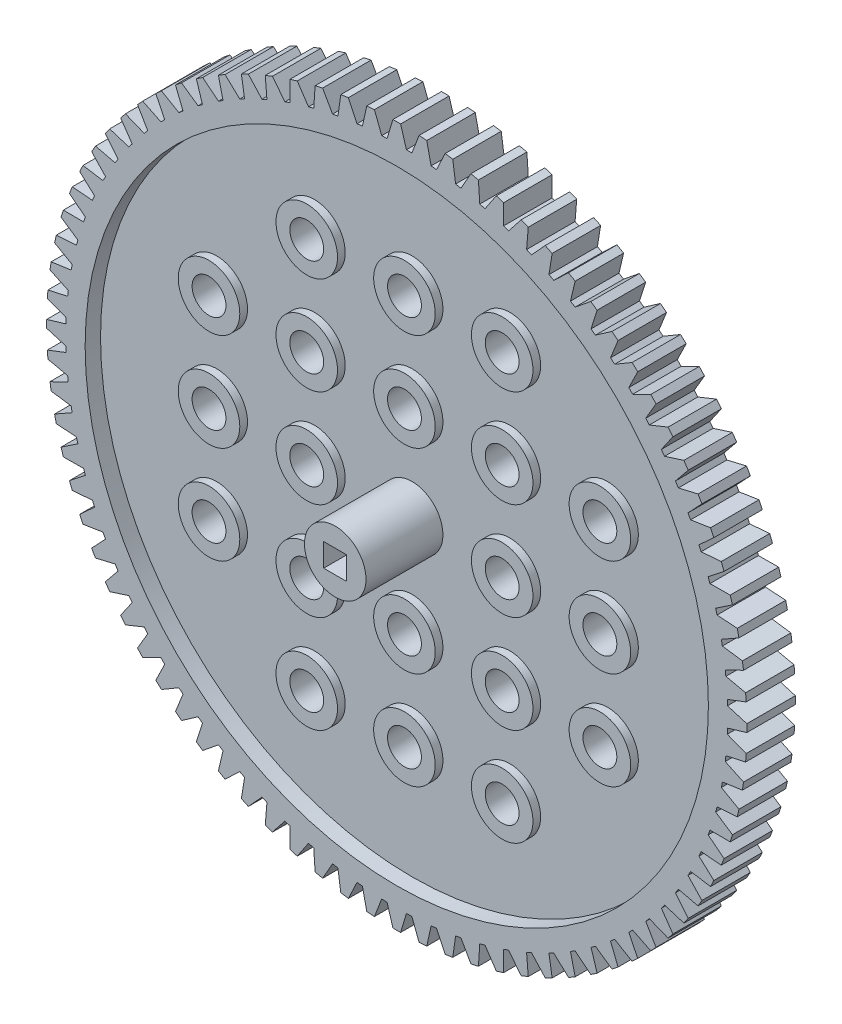
SolidWorks part; units mm, degrees
ref_plane "Front Plane" through (0, 0, 0) normal (0, 0, 1) x (1, 0, 0)
ref_plane "Top Plane" through (0, 0, 0) normal (0, 1, 0) x (1, 0, 0)
ref_plane "Right Plane" through (0, 0, 0) normal (1, 0, 0) x (0, 0, -1)
sketch "Sketch1" plane through (0, 0, 0) normal (0, 0, 1) x (1, 0, 0)
  line L0 (0, 45.5) -> (0, 43)
  line L1 (1.5, -1.5) -> (-1.5, -1.5)
  line L2 (1.5, -1.5) -> (1.5, 1.5)
  line L3 (1.5, 1.5) -> (-1.5, 1.5)
  line L4 (-1.5, -1.5) -> (-1.5, 1.5)
  line L5 (1.5, -1.5) -> (-1.5, 1.5) construction
  line L6 (1.5, 1.5) -> (-1.5, -1.5) construction
  line L7 (-1.25, 43) -> (1.25, 43) construction
  line L8 (-0.5, 45.5) -> (0.5, 45.5)
  line L9 (-1.25, 43) -> (-0.5, 45.5)
  line L10 (1.25, 43) -> (0.5, 45.5)
  line L11 (-1.25, 43) -> (-1.2555, 42.9817)
  line L12 (1.25, 43) -> (1.2555, 42.9817)
  line L13 (1.9669, 42.9732) -> (2.9016, 45.4101)
  line L14 (2.9016, 45.4101) -> (3.8988, 45.3354)
  line L15 (4.4599, 42.7864) -> (3.8988, 45.3354)
  line L16 (1.9669, 42.9732) -> (1.96, 42.9553)
  line L17 (4.4599, 42.7864) -> (4.464, 42.7677)
  line L18 (5.1728, 42.706) -> (6.287, 45.0663)
  line L19 (6.287, 45.0663) -> (7.2758, 44.9173)
  line L20 (7.6449, 42.3334) -> (7.2758, 44.9173)
  line L21 (5.1728, 42.706) -> (5.1646, 42.6887)
  line L22 (7.6449, 42.3334) -> (7.6476, 42.3145)
  line L23 (8.3497, 42.2001) -> (9.6372, 44.4705)
  line L24 (9.6372, 44.4705) -> (10.6122, 44.248)
  line L25 (10.7871, 41.6437) -> (10.6122, 44.248)
  line L26 (8.3497, 42.2001) -> (8.3403, 42.1834)
  line L27 (10.7871, 41.6437) -> (10.7883, 41.6247)
  line L28 (11.48, 41.4581) -> (12.9336, 43.6259)
  line L29 (12.9336, 43.6259) -> (13.8891, 43.3312)
  line L30 (13.8689, 40.7212) -> (13.8891, 43.3312)
  line L31 (11.48, 41.4581) -> (11.4693, 41.4422)
  line L32 (13.8689, 40.7212) -> (13.8688, 40.702)
  line L33 (14.5461, 40.4842) -> (16.1576, 42.5374)
  line L34 (16.1576, 42.5374) -> (17.0885, 42.1721)
  line L35 (16.8733, 39.5709) -> (17.0885, 42.1721)
  line L36 (14.5461, 40.4842) -> (14.5343, 40.4692)
  line L37 (16.8733, 39.5709) -> (16.8717, 39.5518)
  line L38 (17.5308, 39.284) -> (19.2912, 41.211)
  line L39 (19.2912, 41.211) -> (20.1922, 40.7771)
  line L40 (19.7832, 38.1993) -> (20.1922, 40.7771)
  line L41 (17.5308, 39.284) -> (17.5179, 39.2699)
  line L42 (19.7832, 38.1993) -> (19.7802, 38.1804)
  line L43 (20.4175, 37.8641) -> (22.317, 39.6542)
  line L44 (22.317, 39.6542) -> (23.183, 39.1542)
  line L45 (22.5825, 36.6141) -> (23.183, 39.1542)
  line L46 (20.4175, 37.8641) -> (20.4035, 37.851)
  line L47 (22.5825, 36.6141) -> (22.5781, 36.5955)
  line L48 (23.19, 36.2324) -> (25.2179, 37.8755)
  line L49 (25.2179, 37.8755) -> (26.0442, 37.3122)
  line L50 (25.2556, 34.8241) -> (26.0442, 37.3122)
  line L51 (23.19, 36.2324) -> (23.1751, 36.2204)
  line L52 (25.2556, 34.8241) -> (25.2498, 34.8059)
  line L53 (25.8328, 34.3981) -> (27.9779, 35.8851)
  line L54 (27.9779, 35.8851) -> (28.7597, 35.2616)
  line L55 (27.7874, 32.8394) -> (28.7597, 35.2616)
  line L56 (25.8328, 34.3981) -> (25.817, 34.3872)
  line L57 (27.7874, 32.8394) -> (27.7802, 32.8216)
  line L58 (28.3311, 32.3714) -> (30.5813, 33.6939)
  line L59 (30.5813, 33.6939) -> (31.3144, 33.0138)
  line L60 (30.1637, 30.671) -> (31.3144, 33.0138)
  line L61 (28.3311, 32.3714) -> (28.3146, 32.3617)
  line L62 (30.1637, 30.671) -> (30.1553, 30.6538)
  line L63 (30.671, 30.1637) -> (33.0138, 31.3144)
  line L64 (33.0138, 31.3144) -> (33.6939, 30.5813)
  line L65 (32.3714, 28.3311) -> (33.6939, 30.5813)
  line L66 (30.671, 30.1637) -> (30.6538, 30.1553)
  line L67 (32.3714, 28.3311) -> (32.3617, 28.3146)
  line L68 (32.8394, 27.7874) -> (35.2616, 28.7597)
  line L69 (35.2616, 28.7597) -> (35.8851, 27.9779)
  line L70 (34.3981, 25.8328) -> (35.8851, 27.9779)
  line L71 (32.8394, 27.7874) -> (32.8216, 27.7802)
  line L72 (34.3981, 25.8328) -> (34.3872, 25.817)
  line L73 (34.8241, 25.2556) -> (37.3122, 26.0442)
  line L74 (37.3122, 26.0442) -> (37.8755, 25.2179)
  line L75 (36.2324, 23.19) -> (37.8755, 25.2179)
  line L76 (34.8241, 25.2556) -> (34.8059, 25.2498)
  line L77 (36.2324, 23.19) -> (36.2204, 23.1751)
  line L78 (36.6141, 22.5825) -> (39.1542, 23.183)
  line L79 (39.1542, 23.183) -> (39.6542, 22.317)
  line L80 (37.8641, 20.4175) -> (39.6542, 22.317)
  line L81 (36.6141, 22.5825) -> (36.5955, 22.5781)
  line L82 (37.8641, 20.4175) -> (37.851, 20.4035)
  line L83 (38.1993, 19.7832) -> (40.7771, 20.1922)
  line L84 (40.7771, 20.1922) -> (41.211, 19.2912)
  line L85 (39.284, 17.5308) -> (41.211, 19.2912)
  line L86 (38.1993, 19.7832) -> (38.1804, 19.7802)
  line L87 (39.284, 17.5308) -> (39.2699, 17.5179)
  line L88 (39.5709, 16.8733) -> (42.1721, 17.0885)
  line L89 (42.1721, 17.0885) -> (42.5374, 16.1576)
  line L90 (40.4842, 14.5461) -> (42.5374, 16.1576)
  line L91 (39.5709, 16.8733) -> (39.5518, 16.8717)
  line L92 (40.4842, 14.5461) -> (40.4692, 14.5343)
  line L93 (40.7212, 13.8689) -> (43.3312, 13.8891)
  line L94 (43.3312, 13.8891) -> (43.6259, 12.9336)
  line L95 (41.4581, 11.48) -> (43.6259, 12.9336)
  line L96 (40.7212, 13.8689) -> (40.702, 13.8688)
  line L97 (41.4581, 11.48) -> (41.4422, 11.4693)
  line L98 (41.6437, 10.7871) -> (44.248, 10.6122)
  line L99 (44.248, 10.6122) -> (44.4705, 9.6372)
  line L100 (42.2001, 8.3497) -> (44.4705, 9.6372)
  line L101 (41.6437, 10.7871) -> (41.6247, 10.7883)
  line L102 (42.2001, 8.3497) -> (42.1834, 8.3403)
  line L103 (42.3334, 7.6449) -> (44.9173, 7.2758)
  line L104 (44.9173, 7.2758) -> (45.0663, 6.287)
  line L105 (42.706, 5.1728) -> (45.0663, 6.287)
  line L106 (42.3334, 7.6449) -> (42.3145, 7.6476)
  line L107 (42.706, 5.1728) -> (42.6887, 5.1646)
  line L108 (42.7864, 4.4599) -> (45.3354, 3.8988)
  line L109 (45.3354, 3.8988) -> (45.4101, 2.9016)
  line L110 (42.9732, 1.9669) -> (45.4101, 2.9016)
  line L111 (42.7864, 4.4599) -> (42.7677, 4.464)
  line L112 (42.9732, 1.9669) -> (42.9553, 1.96)
  line L113 (43, 1.25) -> (45.5, 0.5)
  line L114 (45.5, 0.5) -> (45.5, -0.5)
  line L115 (43, -1.25) -> (45.5, -0.5)
  line L116 (43, 1.25) -> (42.9817, 1.2555)
  line L117 (43, -1.25) -> (42.9817, -1.2555)
  line L118 (42.9732, -1.9669) -> (45.4101, -2.9016)
  line L119 (45.4101, -2.9016) -> (45.3354, -3.8988)
  line L120 (42.7864, -4.4599) -> (45.3354, -3.8988)
  line L121 (42.9732, -1.9669) -> (42.9553, -1.96)
  line L122 (42.7864, -4.4599) -> (42.7677, -4.464)
  line L123 (42.706, -5.1728) -> (45.0663, -6.287)
  line L124 (45.0663, -6.287) -> (44.9173, -7.2758)
  line L125 (42.3334, -7.6449) -> (44.9173, -7.2758)
  line L126 (42.706, -5.1728) -> (42.6887, -5.1646)
  line L127 (42.3334, -7.6449) -> (42.3145, -7.6476)
  line L128 (42.2001, -8.3497) -> (44.4705, -9.6372)
  line L129 (44.4705, -9.6372) -> (44.248, -10.6122)
  line L130 (41.6437, -10.7871) -> (44.248, -10.6122)
  line L131 (42.2001, -8.3497) -> (42.1834, -8.3403)
  line L132 (41.6437, -10.7871) -> (41.6247, -10.7883)
  line L133 (41.4581, -11.48) -> (43.6259, -12.9336)
  line L134 (43.6259, -12.9336) -> (43.3312, -13.8891)
  line L135 (40.7212, -13.8689) -> (43.3312, -13.8891)
  line L136 (41.4581, -11.48) -> (41.4422, -11.4693)
  line L137 (40.7212, -13.8689) -> (40.702, -13.8688)
  line L138 (40.4842, -14.5461) -> (42.5374, -16.1576)
  line L139 (42.5374, -16.1576) -> (42.1721, -17.0885)
  line L140 (39.5709, -16.8733) -> (42.1721, -17.0885)
  line L141 (40.4842, -14.5461) -> (40.4692, -14.5343)
  line L142 (39.5709, -16.8733) -> (39.5518, -16.8717)
  line L143 (39.284, -17.5308) -> (41.211, -19.2912)
  line L144 (41.211, -19.2912) -> (40.7771, -20.1922)
  line L145 (38.1993, -19.7832) -> (40.7771, -20.1922)
  line L146 (39.284, -17.5308) -> (39.2699, -17.5179)
  line L147 (38.1993, -19.7832) -> (38.1804, -19.7802)
  line L148 (37.8641, -20.4175) -> (39.6542, -22.317)
  line L149 (39.6542, -22.317) -> (39.1542, -23.183)
  line L150 (36.6141, -22.5825) -> (39.1542, -23.183)
  line L151 (37.8641, -20.4175) -> (37.851, -20.4035)
  line L152 (36.6141, -22.5825) -> (36.5955, -22.5781)
  line L153 (36.2324, -23.19) -> (37.8755, -25.2179)
  line L154 (37.8755, -25.2179) -> (37.3122, -26.0442)
  line L155 (34.8241, -25.2556) -> (37.3122, -26.0442)
  line L156 (36.2324, -23.19) -> (36.2204, -23.1751)
  line L157 (34.8241, -25.2556) -> (34.8059, -25.2498)
  line L158 (34.3981, -25.8328) -> (35.8851, -27.9779)
  line L159 (35.8851, -27.9779) -> (35.2616, -28.7597)
  line L160 (32.8394, -27.7874) -> (35.2616, -28.7597)
  line L161 (34.3981, -25.8328) -> (34.3872, -25.817)
  line L162 (32.8394, -27.7874) -> (32.8216, -27.7802)
  line L163 (32.3714, -28.3311) -> (33.6939, -30.5813)
  line L164 (33.6939, -30.5813) -> (33.0138, -31.3144)
  line L165 (30.671, -30.1637) -> (33.0138, -31.3144)
  line L166 (32.3714, -28.3311) -> (32.3617, -28.3146)
  line L167 (30.671, -30.1637) -> (30.6538, -30.1553)
  line L168 (30.1637, -30.671) -> (31.3144, -33.0138)
  line L169 (31.3144, -33.0138) -> (30.5813, -33.6939)
  line L170 (28.3311, -32.3714) -> (30.5813, -33.6939)
  line L171 (30.1637, -30.671) -> (30.1553, -30.6538)
  line L172 (28.3311, -32.3714) -> (28.3146, -32.3617)
  line L173 (27.7874, -32.8394) -> (28.7597, -35.2616)
  line L174 (28.7597, -35.2616) -> (27.9779, -35.8851)
  line L175 (25.8328, -34.3981) -> (27.9779, -35.8851)
  line L176 (27.7874, -32.8394) -> (27.7802, -32.8216)
  line L177 (25.8328, -34.3981) -> (25.817, -34.3872)
  line L178 (25.2556, -34.8241) -> (26.0442, -37.3122)
  line L179 (26.0442, -37.3122) -> (25.2179, -37.8755)
  line L180 (23.19, -36.2324) -> (25.2179, -37.8755)
  line L181 (25.2556, -34.8241) -> (25.2498, -34.8059)
  line L182 (23.19, -36.2324) -> (23.1751, -36.2204)
  line L183 (22.5825, -36.6141) -> (23.183, -39.1542)
  line L184 (23.183, -39.1542) -> (22.317, -39.6542)
  line L185 (20.4175, -37.8641) -> (22.317, -39.6542)
  line L186 (22.5825, -36.6141) -> (22.5781, -36.5955)
  line L187 (20.4175, -37.8641) -> (20.4035, -37.851)
  line L188 (19.7832, -38.1993) -> (20.1922, -40.7771)
  line L189 (20.1922, -40.7771) -> (19.2912, -41.211)
  line L190 (17.5308, -39.284) -> (19.2912, -41.211)
  line L191 (19.7832, -38.1993) -> (19.7802, -38.1804)
  line L192 (17.5308, -39.284) -> (17.5179, -39.2699)
  line L193 (16.8733, -39.5709) -> (17.0885, -42.1721)
  line L194 (17.0885, -42.1721) -> (16.1576, -42.5374)
  line L195 (14.5461, -40.4842) -> (16.1576, -42.5374)
  line L196 (16.8733, -39.5709) -> (16.8717, -39.5518)
  line L197 (14.5461, -40.4842) -> (14.5343, -40.4692)
  line L198 (13.8689, -40.7212) -> (13.8891, -43.3312)
  line L199 (13.8891, -43.3312) -> (12.9336, -43.6259)
  line L200 (11.48, -41.4581) -> (12.9336, -43.6259)
  line L201 (13.8689, -40.7212) -> (13.8688, -40.702)
  line L202 (11.48, -41.4581) -> (11.4693, -41.4422)
  line L203 (10.7871, -41.6437) -> (10.6122, -44.248)
  line L204 (10.6122, -44.248) -> (9.6372, -44.4705)
  line L205 (8.3497, -42.2001) -> (9.6372, -44.4705)
  line L206 (10.7871, -41.6437) -> (10.7883, -41.6247)
  line L207 (8.3497, -42.2001) -> (8.3403, -42.1834)
  line L208 (7.6449, -42.3334) -> (7.2758, -44.9173)
  line L209 (7.2758, -44.9173) -> (6.287, -45.0663)
  line L210 (5.1728, -42.706) -> (6.287, -45.0663)
  line L211 (7.6449, -42.3334) -> (7.6476, -42.3145)
  line L212 (5.1728, -42.706) -> (5.1646, -42.6887)
  line L213 (4.4599, -42.7864) -> (3.8988, -45.3354)
  line L214 (3.8988, -45.3354) -> (2.9016, -45.4101)
  line L215 (1.9669, -42.9732) -> (2.9016, -45.4101)
  line L216 (4.4599, -42.7864) -> (4.464, -42.7677)
  line L217 (1.9669, -42.9732) -> (1.96, -42.9553)
  line L218 (1.25, -43) -> (0.5, -45.5)
  line L219 (0.5, -45.5) -> (-0.5, -45.5)
  line L220 (-1.25, -43) -> (-0.5, -45.5)
  line L221 (1.25, -43) -> (1.2555, -42.9817)
  line L222 (-1.25, -43) -> (-1.2555, -42.9817)
  line L223 (-1.9669, -42.9732) -> (-2.9016, -45.4101)
  line L224 (-2.9016, -45.4101) -> (-3.8988, -45.3354)
  line L225 (-4.4599, -42.7864) -> (-3.8988, -45.3354)
  line L226 (-1.9669, -42.9732) -> (-1.96, -42.9553)
  line L227 (-4.4599, -42.7864) -> (-4.464, -42.7677)
  line L228 (-5.1728, -42.706) -> (-6.287, -45.0663)
  line L229 (-6.287, -45.0663) -> (-7.2758, -44.9173)
  line L230 (-7.6449, -42.3334) -> (-7.2758, -44.9173)
  line L231 (-5.1728, -42.706) -> (-5.1646, -42.6887)
  line L232 (-7.6449, -42.3334) -> (-7.6476, -42.3145)
  line L233 (-8.3497, -42.2001) -> (-9.6372, -44.4705)
  line L234 (-9.6372, -44.4705) -> (-10.6122, -44.248)
  line L235 (-10.7871, -41.6437) -> (-10.6122, -44.248)
  line L236 (-8.3497, -42.2001) -> (-8.3403, -42.1834)
  line L237 (-10.7871, -41.6437) -> (-10.7883, -41.6247)
  line L238 (-11.48, -41.4581) -> (-12.9336, -43.6259)
  line L239 (-12.9336, -43.6259) -> (-13.8891, -43.3312)
  line L240 (-13.8689, -40.7212) -> (-13.8891, -43.3312)
  line L241 (-11.48, -41.4581) -> (-11.4693, -41.4422)
  line L242 (-13.8689, -40.7212) -> (-13.8688, -40.702)
  line L243 (-14.5461, -40.4842) -> (-16.1576, -42.5374)
  line L244 (-16.1576, -42.5374) -> (-17.0885, -42.1721)
  line L245 (-16.8733, -39.5709) -> (-17.0885, -42.1721)
  line L246 (-14.5461, -40.4842) -> (-14.5343, -40.4692)
  line L247 (-16.8733, -39.5709) -> (-16.8717, -39.5518)
  line L248 (-17.5308, -39.284) -> (-19.2912, -41.211)
  line L249 (-19.2912, -41.211) -> (-20.1922, -40.7771)
  line L250 (-19.7832, -38.1993) -> (-20.1922, -40.7771)
  line L251 (-17.5308, -39.284) -> (-17.5179, -39.2699)
  line L252 (-19.7832, -38.1993) -> (-19.7802, -38.1804)
  line L253 (-20.4175, -37.8641) -> (-22.317, -39.6542)
  line L254 (-22.317, -39.6542) -> (-23.183, -39.1542)
  line L255 (-22.5825, -36.6141) -> (-23.183, -39.1542)
  line L256 (-20.4175, -37.8641) -> (-20.4035, -37.851)
  line L257 (-22.5825, -36.6141) -> (-22.5781, -36.5955)
  line L258 (-23.19, -36.2324) -> (-25.2179, -37.8755)
  line L259 (-25.2179, -37.8755) -> (-26.0442, -37.3122)
  line L260 (-25.2556, -34.8241) -> (-26.0442, -37.3122)
  line L261 (-23.19, -36.2324) -> (-23.1751, -36.2204)
  line L262 (-25.2556, -34.8241) -> (-25.2498, -34.8059)
  line L263 (-25.8328, -34.3981) -> (-27.9779, -35.8851)
  line L264 (-27.9779, -35.8851) -> (-28.7597, -35.2616)
  line L265 (-27.7874, -32.8394) -> (-28.7597, -35.2616)
  line L266 (-25.8328, -34.3981) -> (-25.817, -34.3872)
  line L267 (-27.7874, -32.8394) -> (-27.7802, -32.8216)
  line L268 (-28.3311, -32.3714) -> (-30.5813, -33.6939)
  line L269 (-30.5813, -33.6939) -> (-31.3144, -33.0138)
  line L270 (-30.1637, -30.671) -> (-31.3144, -33.0138)
  line L271 (-28.3311, -32.3714) -> (-28.3146, -32.3617)
  line L272 (-30.1637, -30.671) -> (-30.1553, -30.6538)
  line L273 (-30.671, -30.1637) -> (-33.0138, -31.3144)
  line L274 (-33.0138, -31.3144) -> (-33.6939, -30.5813)
  line L275 (-32.3714, -28.3311) -> (-33.6939, -30.5813)
  line L276 (-30.671, -30.1637) -> (-30.6538, -30.1553)
  line L277 (-32.3714, -28.3311) -> (-32.3617, -28.3146)
  line L278 (-32.8394, -27.7874) -> (-35.2616, -28.7597)
  line L279 (-35.2616, -28.7597) -> (-35.8851, -27.9779)
  line L280 (-34.3981, -25.8328) -> (-35.8851, -27.9779)
  line L281 (-32.8394, -27.7874) -> (-32.8216, -27.7802)
  line L282 (-34.3981, -25.8328) -> (-34.3872, -25.817)
  line L283 (-34.8241, -25.2556) -> (-37.3122, -26.0442)
  line L284 (-37.3122, -26.0442) -> (-37.8755, -25.2179)
  line L285 (-36.2324, -23.19) -> (-37.8755, -25.2179)
  line L286 (-34.8241, -25.2556) -> (-34.8059, -25.2498)
  line L287 (-36.2324, -23.19) -> (-36.2204, -23.1751)
  line L288 (-36.6141, -22.5825) -> (-39.1542, -23.183)
  line L289 (-39.1542, -23.183) -> (-39.6542, -22.317)
  line L290 (-37.8641, -20.4175) -> (-39.6542, -22.317)
  line L291 (-36.6141, -22.5825) -> (-36.5955, -22.5781)
  line L292 (-37.8641, -20.4175) -> (-37.851, -20.4035)
  line L293 (-38.1993, -19.7832) -> (-40.7771, -20.1922)
  line L294 (-40.7771, -20.1922) -> (-41.211, -19.2912)
  line L295 (-39.284, -17.5308) -> (-41.211, -19.2912)
  line L296 (-38.1993, -19.7832) -> (-38.1804, -19.7802)
  line L297 (-39.284, -17.5308) -> (-39.2699, -17.5179)
  line L298 (-39.5709, -16.8733) -> (-42.1721, -17.0885)
  line L299 (-42.1721, -17.0885) -> (-42.5374, -16.1576)
  line L300 (-40.4842, -14.5461) -> (-42.5374, -16.1576)
  line L301 (-39.5709, -16.8733) -> (-39.5518, -16.8717)
  line L302 (-40.4842, -14.5461) -> (-40.4692, -14.5343)
  line L303 (-40.7212, -13.8689) -> (-43.3312, -13.8891)
  line L304 (-43.3312, -13.8891) -> (-43.6259, -12.9336)
  line L305 (-41.4581, -11.48) -> (-43.6259, -12.9336)
  line L306 (-40.7212, -13.8689) -> (-40.702, -13.8688)
  line L307 (-41.4581, -11.48) -> (-41.4422, -11.4693)
  line L308 (-41.6437, -10.7871) -> (-44.248, -10.6122)
  line L309 (-44.248, -10.6122) -> (-44.4705, -9.6372)
  line L310 (-42.2001, -8.3497) -> (-44.4705, -9.6372)
  line L311 (-41.6437, -10.7871) -> (-41.6247, -10.7883)
  line L312 (-42.2001, -8.3497) -> (-42.1834, -8.3403)
  line L313 (-42.3334, -7.6449) -> (-44.9173, -7.2758)
  line L314 (-44.9173, -7.2758) -> (-45.0663, -6.287)
  line L315 (-42.706, -5.1728) -> (-45.0663, -6.287)
  line L316 (-42.3334, -7.6449) -> (-42.3145, -7.6476)
  line L317 (-42.706, -5.1728) -> (-42.6887, -5.1646)
  line L318 (-42.7864, -4.4599) -> (-45.3354, -3.8988)
  line L319 (-45.3354, -3.8988) -> (-45.4101, -2.9016)
  line L320 (-42.9732, -1.9669) -> (-45.4101, -2.9016)
  line L321 (-42.7864, -4.4599) -> (-42.7677, -4.464)
  line L322 (-42.9732, -1.9669) -> (-42.9553, -1.96)
  line L323 (-43, -1.25) -> (-45.5, -0.5)
  line L324 (-45.5, -0.5) -> (-45.5, 0.5)
  line L325 (-43, 1.25) -> (-45.5, 0.5)
  line L326 (-43, -1.25) -> (-42.9817, -1.2555)
  line L327 (-43, 1.25) -> (-42.9817, 1.2555)
  line L328 (-42.9732, 1.9669) -> (-45.4101, 2.9016)
  line L329 (-45.4101, 2.9016) -> (-45.3354, 3.8988)
  line L330 (-42.7864, 4.4599) -> (-45.3354, 3.8988)
  line L331 (-42.9732, 1.9669) -> (-42.9553, 1.96)
  line L332 (-42.7864, 4.4599) -> (-42.7677, 4.464)
  line L333 (-42.706, 5.1728) -> (-45.0663, 6.287)
  line L334 (-45.0663, 6.287) -> (-44.9173, 7.2758)
  line L335 (-42.3334, 7.6449) -> (-44.9173, 7.2758)
  line L336 (-42.706, 5.1728) -> (-42.6887, 5.1646)
  line L337 (-42.3334, 7.6449) -> (-42.3145, 7.6476)
  line L338 (-42.2001, 8.3497) -> (-44.4705, 9.6372)
  line L339 (-44.4705, 9.6372) -> (-44.248, 10.6122)
  line L340 (-41.6437, 10.7871) -> (-44.248, 10.6122)
  line L341 (-42.2001, 8.3497) -> (-42.1834, 8.3403)
  line L342 (-41.6437, 10.7871) -> (-41.6247, 10.7883)
  line L343 (-41.4581, 11.48) -> (-43.6259, 12.9336)
  line L344 (-43.6259, 12.9336) -> (-43.3312, 13.8891)
  line L345 (-40.7212, 13.8689) -> (-43.3312, 13.8891)
  line L346 (-41.4581, 11.48) -> (-41.4422, 11.4693)
  line L347 (-40.7212, 13.8689) -> (-40.702, 13.8688)
  line L348 (-40.4842, 14.5461) -> (-42.5374, 16.1576)
  line L349 (-42.5374, 16.1576) -> (-42.1721, 17.0885)
  line L350 (-39.5709, 16.8733) -> (-42.1721, 17.0885)
  line L351 (-40.4842, 14.5461) -> (-40.4692, 14.5343)
  line L352 (-39.5709, 16.8733) -> (-39.5518, 16.8717)
  line L353 (-39.284, 17.5308) -> (-41.211, 19.2912)
  line L354 (-41.211, 19.2912) -> (-40.7771, 20.1922)
  line L355 (-38.1993, 19.7832) -> (-40.7771, 20.1922)
  line L356 (-39.284, 17.5308) -> (-39.2699, 17.5179)
  line L357 (-38.1993, 19.7832) -> (-38.1804, 19.7802)
  line L358 (-37.8641, 20.4175) -> (-39.6542, 22.317)
  line L359 (-39.6542, 22.317) -> (-39.1542, 23.183)
  line L360 (-36.6141, 22.5825) -> (-39.1542, 23.183)
  line L361 (-37.8641, 20.4175) -> (-37.851, 20.4035)
  line L362 (-36.6141, 22.5825) -> (-36.5955, 22.5781)
  line L363 (-36.2324, 23.19) -> (-37.8755, 25.2179)
  line L364 (-37.8755, 25.2179) -> (-37.3122, 26.0442)
  line L365 (-34.8241, 25.2556) -> (-37.3122, 26.0442)
  line L366 (-36.2324, 23.19) -> (-36.2204, 23.1751)
  line L367 (-34.8241, 25.2556) -> (-34.8059, 25.2498)
  line L368 (-34.3981, 25.8328) -> (-35.8851, 27.9779)
  line L369 (-35.8851, 27.9779) -> (-35.2616, 28.7597)
  line L370 (-32.8394, 27.7874) -> (-35.2616, 28.7597)
  line L371 (-34.3981, 25.8328) -> (-34.3872, 25.817)
  line L372 (-32.8394, 27.7874) -> (-32.8216, 27.7802)
  line L373 (-32.3714, 28.3311) -> (-33.6939, 30.5813)
  line L374 (-33.6939, 30.5813) -> (-33.0138, 31.3144)
  line L375 (-30.671, 30.1637) -> (-33.0138, 31.3144)
  line L376 (-32.3714, 28.3311) -> (-32.3617, 28.3146)
  line L377 (-30.671, 30.1637) -> (-30.6538, 30.1553)
  line L378 (-30.1637, 30.671) -> (-31.3144, 33.0138)
  line L379 (-31.3144, 33.0138) -> (-30.5813, 33.6939)
  line L380 (-28.3311, 32.3714) -> (-30.5813, 33.6939)
  line L381 (-30.1637, 30.671) -> (-30.1553, 30.6538)
  line L382 (-28.3311, 32.3714) -> (-28.3146, 32.3617)
  line L383 (-27.7874, 32.8394) -> (-28.7597, 35.2616)
  line L384 (-28.7597, 35.2616) -> (-27.9779, 35.8851)
  line L385 (-25.8328, 34.3981) -> (-27.9779, 35.8851)
  line L386 (-27.7874, 32.8394) -> (-27.7802, 32.8216)
  line L387 (-25.8328, 34.3981) -> (-25.817, 34.3872)
  line L388 (-25.2556, 34.8241) -> (-26.0442, 37.3122)
  line L389 (-26.0442, 37.3122) -> (-25.2179, 37.8755)
  line L390 (-23.19, 36.2324) -> (-25.2179, 37.8755)
  line L391 (-25.2556, 34.8241) -> (-25.2498, 34.8059)
  line L392 (-23.19, 36.2324) -> (-23.1751, 36.2204)
  line L393 (-22.5825, 36.6141) -> (-23.183, 39.1542)
  line L394 (-23.183, 39.1542) -> (-22.317, 39.6542)
  line L395 (-20.4175, 37.8641) -> (-22.317, 39.6542)
  line L396 (-22.5825, 36.6141) -> (-22.5781, 36.5955)
  line L397 (-20.4175, 37.8641) -> (-20.4035, 37.851)
  line L398 (-19.7832, 38.1993) -> (-20.1922, 40.7771)
  line L399 (-20.1922, 40.7771) -> (-19.2912, 41.211)
  line L400 (-17.5308, 39.284) -> (-19.2912, 41.211)
  line L401 (-19.7832, 38.1993) -> (-19.7802, 38.1804)
  line L402 (-17.5308, 39.284) -> (-17.5179, 39.2699)
  line L403 (-16.8733, 39.5709) -> (-17.0885, 42.1721)
  line L404 (-17.0885, 42.1721) -> (-16.1576, 42.5374)
  line L405 (-14.5461, 40.4842) -> (-16.1576, 42.5374)
  line L406 (-16.8733, 39.5709) -> (-16.8717, 39.5518)
  line L407 (-14.5461, 40.4842) -> (-14.5343, 40.4692)
  line L408 (-13.8689, 40.7212) -> (-13.8891, 43.3312)
  line L409 (-13.8891, 43.3312) -> (-12.9336, 43.6259)
  line L410 (-11.48, 41.4581) -> (-12.9336, 43.6259)
  line L411 (-13.8689, 40.7212) -> (-13.8688, 40.702)
  line L412 (-11.48, 41.4581) -> (-11.4693, 41.4422)
  line L413 (-10.7871, 41.6437) -> (-10.6122, 44.248)
  line L414 (-10.6122, 44.248) -> (-9.6372, 44.4705)
  line L415 (-8.3497, 42.2001) -> (-9.6372, 44.4705)
  line L416 (-10.7871, 41.6437) -> (-10.7883, 41.6247)
  line L417 (-8.3497, 42.2001) -> (-8.3403, 42.1834)
  line L418 (-7.6449, 42.3334) -> (-7.2758, 44.9173)
  line L419 (-7.2758, 44.9173) -> (-6.287, 45.0663)
  line L420 (-5.1728, 42.706) -> (-6.287, 45.0663)
  line L421 (-7.6449, 42.3334) -> (-7.6476, 42.3145)
  line L422 (-5.1728, 42.706) -> (-5.1646, 42.6887)
  line L423 (-4.4599, 42.7864) -> (-3.8988, 45.3354)
  line L424 (-3.8988, 45.3354) -> (-2.9016, 45.4101)
  line L425 (-1.9669, 42.9732) -> (-2.9016, 45.4101)
  line L426 (-4.4599, 42.7864) -> (-4.464, 42.7677)
  line L427 (-1.9669, 42.9732) -> (-1.96, 42.9553)
  circle A0 centre (0, 0) radius 45.5 construction
  circle A1 centre (0, 0) radius 40.5
  circle A2 centre (0, 0) radius 43
  point P0 (0, 0)
  point P13 (0, 45.5)
  point P15 (0, 43)
  point P521 (0, 0)
  dimension "D2" = 91
  dimension "D3" = 81
  dimension "D1" = 3
  dimension "D4" = 2.5
  dimension "D5" = 2.5
  dimension "D6" = 1
  dimension "D7" = 84
extrude "Boss-Extrude1" add sketch "Sketch1" along normal blind 6.3 contours A2 L232 L230 L229 L228 L231 | A2 L227 L225 L224 L223 L226 | A2 L222 L220 L219 L218 L221 | A2 L217 L215 L214 L213 L216 | A2 L212 L210 L209 L208 L211 | A2 L207 L205 L204 L203 L206 | A2 L202 L200 L199 L198 L201 | A2 L197 L195 L194 L193 L196 | A2 L192 L190 L189 L188 L191 | A2 L187 L185 L184 L183 L186 | A2 L182 L180 L179 L178 L181 | A2 L177 L175 L174 L173 L176 | A2 L172 L170 L169 L168 L171 | A2 L167 L165 L164 L163 L166 | A2 L162 L160 L159 L158 L161 | A2 L157 L155 L154 L153 L156 | A2 L152 L150 L149 L148 L151 | A2 L147 L145 L144 L143 L146 | A2 L142 L140 L139 L138 L141 | A2 L137 L135 L134 L133 L136 | A2 L132 L130 L129 L128 L131 | A2 L127 L125 L124 L123 L126 | A2 L122 L120 L119 L118 L121 | A2 L117 L115 L114 L113 L116 | A2 L112 L110 L109 L108 L111 | A2 L107 L105 L104 L103 L106 | A2 L102 L100 L99 L98 L101 | A2 L97 L95 L94 L93 L96 | A2 L92 L90 L89 L88 L91 | A2 L87 L85 L84 L83 L86 | A2 L82 L80 L79 L78 L81 | A2 L77 L75 L74 L73 L76 | A2 L72 L70 L69 L68 L71 | A2 L67 L65 L64 L63 L66 | A2 L62 L60 L59 L58 L61 | A2 L57 L55 L54 L53 L56 | A2 L52 L50 L49 L48 L51 | A2 L47 L45 L44 L43 L46 | A2 L42 L40 L39 L38 L41 | A2 L37 L35 L34 L33 L36 | A2 L32 L30 L29 L28 L31 | A2 L27 L25 L24 L23 L26 | A2 L22 L20 L19 L18 L21 | A2 L17 L15 L14 L13 L16 | A2 L12 L10 L8 L0 | A2 L0 L8 L9 L11 | A2 L427 L425 L424 L423 L426 | A2 L422 L420 L419 L418 L421 | A2 L417 L415 L414 L413 L416 | A2 L412 L410 L409 L408 L411 | A2 L407 L405 L404 L403 L406 | A2 L402 L400 L399 L398 L401 | A2 L397 L395 L394 L393 L396 | A2 L392 L390 L389 L388 L391 | A2 L387 L385 L384 L383 L386 | A2 L382 L380 L379 L378 L381 | A2 L377 L375 L374 L373 L376 | A2 L372 L370 L369 L368 L371 | A2 L367 L365 L364 L363 L366 | A2 L362 L360 L359 L358 L361 | A2 L357 L355 L354 L353 L356 | A2 L352 L350 L349 L348 L351 | A2 L347 L345 L344 L343 L346 | A2 L342 L340 L339 L338 L341 | A2 L337 L335 L334 L333 L336 | A2 L332 L330 L329 L328 L331 | A2 L327 L325 L324 L323 L326 | A2 L322 L320 L319 L318 L321 | A2 L317 L315 L314 L313 L316 | A2 L312 L310 L309 L308 L311 | A2 L307 L305 L304 L303 L306 | A2 L302 L300 L299 L298 L301 | A2 L297 L295 L294 L293 L296 | A2 L292 L290 L289 L288 L291 | A2 L287 L285 L284 L283 L286 | A2 L282 L280 L279 L278 L281 | A2 L277 L275 L274 L273 L276 | A2 L272 L270 L269 L268 L271 | A2 L267 L265 L264 L263 L266 | A2 L262 L260 L259 L258 L261 | A2 L257 L255 L254 L253 L256 | A2 L252 L250 L249 L248 L251 | A2 L247 L245 L244 L243 L246 | A2 L242 L240 L239 L238 L241 | A2 L237 L235 L234 L233 L236 | A1 L1 L4 L3 L2 | A2 L3 region at (0.4659, 44.0677, 0) region at (-0.4659, 44.0677, 0) region at (0.6101, 41.7793, 0) region at (3.2932, 43.9445, 0) region at (-3.2932, 43.9445, 0) region at (6.5679, 43.5755, 0) region at (-6.5679, 43.5755, 0) region at (9.806, 42.9628, 0) region at (-9.806, 42.9628, 0) region at (12.9892, 42.1099, 0) region at (-12.9892, 42.1099, 0) region at (16.0997, 41.0215, 0) region at (-16.0997, 41.0215, 0) region at (19.1203, 39.7036, 0) region at (-19.1203, 39.7036, 0) region at (22.0338, 38.1637, 0) region at (-22.0338, 38.1637, 0) region at (24.8242, 36.4104, 0) region at (-24.8242, 36.4104, 0) region at (27.4758, 34.4535, 0) region at (-27.4758, 34.4535, 0) region at (29.9736, 32.3039, 0) region at (-29.9736, 32.3039, 0) region at (32.3039, 29.9736, 0) region at (-32.3039, 29.9736, 0) region at (34.4535, 27.4758, 0) region at (-34.4535, 27.4758, 0) region at (36.4104, 24.8242, 0) region at (-36.4104, 24.8242, 0) region at (38.1637, 22.0338, 0) region at (-38.1637, 22.0338, 0) region at (39.7036, 19.1203, 0) region at (-39.7036, 19.1203, 0) region at (41.0215, 16.0997, 0) region at (-41.0215, 16.0997, 0) region at (42.1099, 12.9892, 0) region at (-42.1099, 12.9892, 0) region at (42.9628, 9.806, 0) region at (-42.9628, 9.806, 0) region at (43.5755, 6.5679, 0) region at (-43.5755, 6.5679, 0) region at (43.9445, 3.2932, 0) region at (-43.9445, 3.2932, 0) region at (44.0677, 0, 0) region at (-44.0677, 0, 0) region at (-43.9445, -3.2932, 0) region at (43.9445, -3.2932, 0) region at (-43.5755, -6.5679, 0) region at (43.5755, -6.5679, 0) region at (-42.9628, -9.806, 0) region at (42.9628, -9.806, 0) region at (-42.1099, -12.9892, 0) region at (42.1099, -12.9892, 0) region at (-41.0215, -16.0997, 0) region at (41.0215, -16.0997, 0) region at (-39.7036, -19.1203, 0) region at (39.7036, -19.1203, 0) region at (-38.1637, -22.0338, 0) region at (38.1637, -22.0338, 0) region at (-36.4104, -24.8242, 0)
sketch "Sketch2" plane through (0, 0, 6.3) normal (0, 0, 1) x (1, 0, 0)
  circle A0 centre (0, 25.4) radius 2.2
  circle A1 centre (0, 12.7) radius 2.2
  circle A2 centre (0, -12.7) radius 2.2
  circle A3 centre (0, -25.4) radius 2.2
  circle A4 centre (12.7, 25.4) radius 2.2
  circle A5 centre (12.7, 12.7) radius 2.2
  circle A6 centre (12.7, -12.7) radius 2.2
  circle A7 centre (12.7, -25.4) radius 2.2
  circle A8 centre (-12.7, 25.4) radius 2.2
  circle A9 centre (-12.7, 12.7) radius 2.2
  circle A10 centre (-12.7, -12.7) radius 2.2
  circle A11 centre (-12.7, -25.4) radius 2.2
  circle A12 centre (-12.7, 0) radius 2.2
  circle A13 centre (12.7, 0) radius 2.2
  circle A14 centre (-25.4, 0) radius 2.2
  circle A15 centre (25.4, 0) radius 2.2
  circle A16 centre (-25.4, 12.7) radius 2.2
  circle A17 centre (25.4, 12.7) radius 2.2
  circle A18 centre (-25.4, -12.7) radius 2.2
  circle A19 centre (25.4, -12.7) radius 2.2
  dimension "D1" = 4.4
  dimension "D2" = 12.7
  dimension "D12" = 12.7
  dimension "D3" = 12.7
  dimension "D4" = 12.7
  dimension "D5" = 12.7
  dimension "D8" = 12.7
  dimension "D9" = 12.7
  dimension "D10" = 12.7
  dimension "D11" = 12.7
  dimension "D13" = 12.7
  dimension "D6" = 2
  dimension "D7" = 2
  dimension "D14" = 2
  dimension "D15" = 2
  dimension "D16" = 2
  dimension "D17" = 2
extrude "Cut-Extrude1" cut sketch "Sketch2" against normal blind 16.3
sketch "Sketch3" plane through (0, 0, 6.3) normal (0, 0, 1) x (1, 0, 0)
  circle A0 centre (0, 0) radius 40.5
  dimension "D1" = 81
extrude "Cut-Extrude2" cut sketch "Sketch3" against normal blind 2
sketch "Sketch4" plane through (0, 0, 0) normal (0, 0, -1) x (-1, 0, 0)
  circle A0 centre (0, 0) radius 40.5
  dimension "D1" = 81
extrude "Cut-Extrude3" cut sketch "Sketch4" against normal blind 2
sketch "Sketch5" plane through (0, 0, 4.3) normal (0, 0, 1) x (1, 0, 0)
  circle A0 centre (-12.7, 25.4) radius 4
  circle A1 centre (-25.4, 12.7) radius 4
  circle A2 centre (-25.4, 0) radius 4
  circle A3 centre (-25.4, -12.7) radius 4
  circle A4 centre (-12.7, -25.4) radius 4
  circle A5 centre (0, 25.4) radius 4
  circle A6 centre (0, -25.4) radius 4
  circle A7 centre (12.7, 25.4) radius 4
  circle A8 centre (12.7, -25.4) radius 4
  circle A9 centre (-12.7, 12.7) radius 4
  circle A10 centre (-12.7, 0) radius 4
  circle A11 centre (-12.7, -12.7) radius 4
  circle A12 centre (0, 12.7) radius 4
  circle A14 centre (0, -12.7) radius 4
  circle A15 centre (12.7, 12.7) radius 4
  circle A16 centre (12.7, 0) radius 4
  circle A17 centre (12.7, -12.7) radius 4
  circle A18 centre (25.4, 12.7) radius 4
  circle A19 centre (25.4, 0) radius 4
  circle A20 centre (25.4, -12.7) radius 4
  circle A21 centre (-25.4, 12.7) radius 2.2
  circle A22 centre (-12.7, 12.7) radius 2.2
  circle A23 centre (0, 12.7) radius 2.2
  circle A24 centre (12.7, 12.7) radius 2.2
  circle A25 centre (25.4, 12.7) radius 2.2
  circle A26 centre (-12.7, 25.4) radius 2.2
  circle A27 centre (0, 25.4) radius 2.2
  circle A28 centre (12.7, 25.4) radius 2.2
  circle A29 centre (-25.4, 0) radius 2.2
  circle A30 centre (-25.4, -12.7) radius 2.2
  circle A31 centre (-12.7, -25.4) radius 2.2
  circle A32 centre (-12.7, 0) radius 2.2
  circle A33 centre (-12.7, -12.7) radius 2.2
  circle A35 centre (0, -12.7) radius 2.2
  circle A36 centre (12.7, 0) radius 2.2
  circle A37 centre (12.7, -12.7) radius 2.2
  circle A38 centre (25.4, 0) radius 2.2
  circle A39 centre (25.4, -12.7) radius 2.2
  circle A40 centre (0, -25.4) radius 2.2
  circle A41 centre (12.7, -25.4) radius 2.2
  circle A42 centre (0, 0) radius 4 [skipped]
  circle A43 centre (0, 0) radius 2.2 [skipped]
  dimension "D1" = 8
  dimension "D4" = 4.4
  dimension "D7" = 4.4
  dimension "D2" = 3
  dimension "D3" = 5
  dimension "D5" = 5
  dimension "D6" = 5
  dimension "D8" = 3
extrude "Boss-Extrude2" add sketch "Sketch5" along normal blind 1
sketch "Sketch6" plane through (0, 0, 2) normal (0, 0, -1) x (-1, 0, 0)
  circle A0 centre (-12.7, 25.4) radius 5.75
  circle A1 centre (0, 25.4) radius 5.75
  circle A2 centre (12.7, 25.4) radius 5.75
  circle A3 centre (-25.4, 12.7) radius 5.75
  circle A4 centre (-25.4, 0) radius 5.75
  circle A5 centre (-25.4, -12.7) radius 5.75
  circle A6 centre (-12.7, -25.4) radius 5.75
  circle A7 centre (-12.7, 12.7) radius 5.75
  circle A8 centre (-12.7, 0) radius 5.75
  circle A9 centre (-12.7, -12.7) radius 5.75
  circle A10 centre (0, 12.7) radius 5.75
  circle A12 centre (0, -12.7) radius 5.75
  circle A13 centre (12.7, 12.7) radius 5.75
  circle A14 centre (12.7, 0) radius 5.75
  circle A15 centre (12.7, -12.7) radius 5.75
  circle A16 centre (25.4, 12.7) radius 5.75
  circle A17 centre (25.4, 0) radius 5.75
  circle A18 centre (25.4, -12.7) radius 5.75
  circle A19 centre (0, -25.4) radius 5.75
  circle A20 centre (12.7, -25.4) radius 5.75
  circle A21 centre (-12.7, 25.4) radius 4.25
  circle A22 centre (0, 25.4) radius 4.25
  circle A23 centre (12.7, 25.4) radius 4.25
  circle A24 centre (-25.4, 12.7) radius 4.25
  circle A25 centre (-25.4, 0) radius 4.25
  circle A26 centre (-25.4, -12.7) radius 4.25
  circle A27 centre (-12.7, -25.4) radius 4.25
  circle A28 centre (-12.7, 12.7) radius 4.25
  circle A29 centre (-12.7, 0) radius 4.25
  circle A30 centre (-12.7, -12.7) radius 4.25
  circle A31 centre (0, 12.7) radius 4.25
  circle A33 centre (0, -12.7) radius 4.25
  circle A34 centre (12.7, 12.7) radius 4.25
  circle A35 centre (12.7, 0) radius 4.25
  circle A36 centre (12.7, -12.7) radius 4.25
  circle A37 centre (25.4, 12.7) radius 4.25
  circle A38 centre (25.4, 0) radius 4.25
  circle A39 centre (25.4, -12.7) radius 4.25
  circle A40 centre (0, -25.4) radius 4.25
  circle A41 centre (12.7, -25.4) radius 4.25
  circle A43 centre (0, 0) radius 5.75 [skipped]
  dimension "D1" = 11.5
  dimension "D3" = 1.5
  dimension "D2" = 5
extrude "Boss-Extrude3" add sketch "Sketch6" along normal blind 2
sketch "Sketch7" plane through (0, 0, 4.3) normal (0, 0, 1) x (1, 0, 0)
  line L1 (-1.5, 1.5) -> (1.5, 1.5)
  line L2 (-1.5, 1.5) -> (-1.5, -1.5)
  line L3 (-1.5, -1.5) -> (1.5, -1.5)
  line L4 (1.5, 1.5) -> (1.5, -1.5)
  circle A0 centre (0, 0) radius 4
  dimension "D1" = 8
extrude "Boss-Extrude4" add sketch "Sketch7" along normal blind 2
sketch "Sketch8" plane through (0, 0, 2) normal (0, 0, -1) x (-1, 0, 0)
  line L1 (-1.5, 1.5) -> (1.5, 1.5)
  line L2 (-1.5, 1.5) -> (-1.5, -1.5)
  line L3 (-1.5, -1.5) -> (1.5, -1.5)
  line L4 (1.5, 1.5) -> (1.5, -1.5)
  circle A0 centre (0, 0) radius 4
  dimension "D1" = 8
extrude "Boss-Extrude5" add sketch "Sketch8" along normal blind 2
sketch "Sketch9" plane through (0, 0, 6.3) normal (0, 0, 1) x (1, 0, 0)
  line L1 (-1.5, 1.5) -> (1.5, 1.5)
  line L2 (-1.5, 1.5) -> (-1.5, -1.5)
  line L3 (-1.5, -1.5) -> (1.5, -1.5)
  line L4 (1.5, 1.5) -> (1.5, -1.5)
  circle A0 centre (0, 0) radius 4
extrude "Boss-Extrude6" add sketch "Sketch9" along normal blind 8
